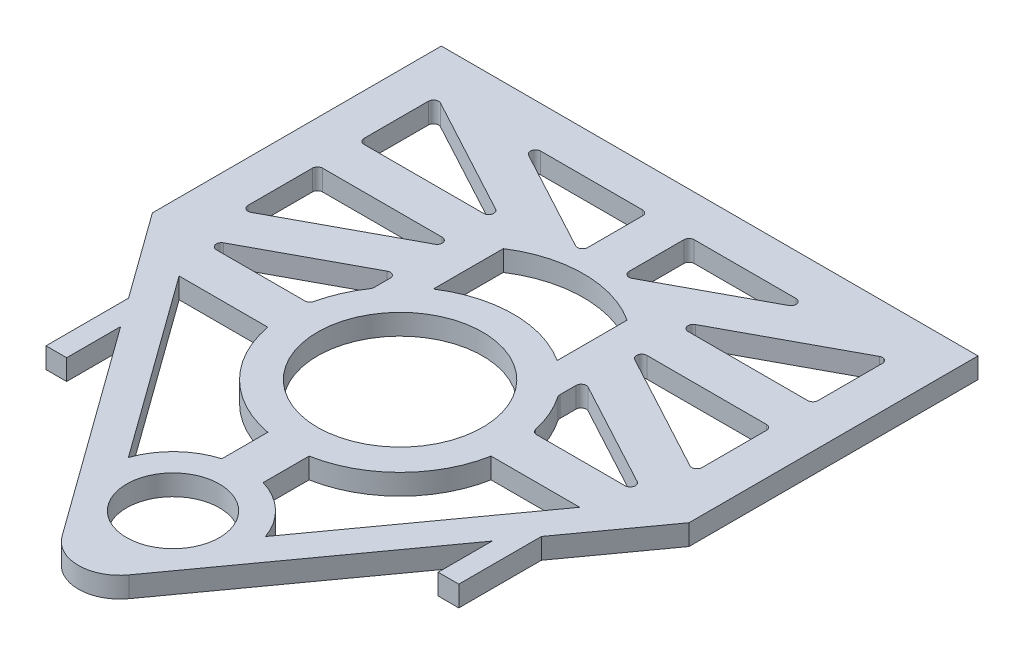
SolidWorks part; units mm, degrees
ref_plane "Front Plane" through (0, 0, 0) normal (0, 0, 1) x (1, 0, 0)
ref_plane "Top Plane" through (0, 0, 0) normal (0, 1, 0) x (1, 0, 0)
ref_plane "Right Plane" through (0, 0, 0) normal (1, 0, 0) x (0, 0, -1)
sketch "Sketch1" plane through (0, 0, 0) normal (0, 1, 0) x (1, 0, 0)
  line L0 (-82.55, -44.45) -> (-10.2956, -144.4945)
  line L2 (-82.55, -44.45) -> (-82.55, 44.45)
  line L3 (-82.55, 44.45) -> (82.55, 44.45)
  line L4 (82.55, -44.45) -> (82.55, 44.45)
  line L5 (-82.55, -44.45) -> (82.55, 44.45) construction
  line L6 (-82.55, 44.45) -> (82.55, -44.45) construction
  line L7 (10.2956, -144.4945) -> (82.55, -44.45)
  line L8 (0, 44.45) -> (0, -158.75) construction
  arc A0 (-10.2956, -144.4945) -> (10.2956, -144.4945) centre (0, -137.0588) ccw
  point P0 (0, 0)
  dimension "D3" = 12.7
  dimension "D1" = 165.1
  dimension "D2" = 88.9
  dimension "D4" = 203.2
extrude "Boss-Extrude1" add sketch "Sketch1" along normal blind 6.35
sketch "Sketch4" plane through (0, 6.35, 0) normal (0, 1, 0) x (1, 0, 0)
  line L0 (-63.5, -70.8269) -> (-63.5, -96.2269)
  line L1 (-82.55, -44.45) -> (-10.2956, -144.4945) construction
  line L2 (0, -149.7588) -> (0, 44.45) construction
  line L3 (82.55, 44.45) -> (-82.55, 44.45) construction
  line L4 (-63.5, -70.8269) -> (-57.15, -79.6192)
  line L5 (-57.15, -79.6192) -> (-57.15, -96.2269)
  line L6 (-57.15, -96.2269) -> (-63.5, -96.2269)
  line L7 (57.15, -96.2269) -> (63.5, -96.2269)
  line L8 (57.15, -79.6192) -> (57.15, -96.2269)
  line L9 (63.5, -70.8269) -> (57.15, -79.6192)
  line L10 (63.5, -70.8269) -> (63.5, -96.2269)
  arc A0 (-10.2956, -144.4945) -> (10.2956, -144.4945) centre (0, -137.0588) ccw construction
  point P18 (0, 0)
  dimension "D1" = 6.35
  dimension "D2" = 25.4
  dimension "D3" = 127
extrude "Boss-Extrude2" add sketch "Sketch4" against normal up to surface (6.35 mm away) up to face at (0, 0, 49.0422)
sketch "Sketch2" plane through (0, 6.35, 0) normal (0, 1, 0) x (1, 0, 0)
  line L0 (-82.55, 0) -> (82.55, 0) construction
  line L1 (-82.55, 44.45) -> (-82.55, -44.45) construction
  line L2 (82.55, -44.45) -> (82.55, 44.45) construction
  line L3 (0, 0) -> (-82.55, 44.45) construction
  line L4 (82.55, 44.45) -> (-82.55, 44.45) construction
  line L5 (0, 44.45) -> (0, -149.7588) construction
  line L6 (-39.2738, 31.75) -> (-7.9375, 31.75)
  line L7 (-6.35, 30.1625) -> (-6.35, 13.2891)
  line L8 (-8.6901, 11.8914) -> (-40.0265, 28.7648)
  line L9 (-69.85, 27.7417) -> (-69.85, 7.9375)
  line L10 (-68.2625, 6.35) -> (-31.4833, 6.35)
  line L11 (-30.7307, 9.3352) -> (-67.5099, 29.1394)
  line L30 (-82.55, -44.45) -> (82.55, -44.45) construction
  line L36 (10.2956, -144.4945) -> (57.15, -79.6192) construction
  line L37 (-51.3603, -50.8) -> (-9.8425, -50.8)
  line L38 (-8.255, -52.3875) -> (-8.255, -98.8766)
  line L39 (-52.6473, -53.317) -> (-16.5965, -103.2335)
  line L40 (-82.55, -44.45) -> (-63.5, -70.8269) construction
  line L41 (51.3603, -50.8) -> (9.8425, -50.8)
  line L42 (8.255, -52.3875) -> (8.255, -98.8766)
  line L43 (52.6473, -53.317) -> (16.5965, -103.2335)
  line L44 (30.7307, 9.3352) -> (67.5099, 29.1394)
  line L45 (68.2625, 6.35) -> (31.4833, 6.35)
  line L46 (69.85, 27.7417) -> (69.85, 7.9375)
  line L47 (6.35, 30.1625) -> (6.35, 13.2891)
  line L48 (8.6901, 11.8914) -> (40.0265, 28.7648)
  line L49 (39.2738, 31.75) -> (7.9375, 31.75)
  line L50 (-30.7307, -9.3352) -> (-67.5099, -29.1394)
  line L51 (-68.2625, -6.35) -> (-31.4833, -6.35)
  line L52 (-69.85, -27.7417) -> (-69.85, -7.9375)
  line L53 (-6.35, -30.1625) -> (-6.35, -13.2891)
  line L54 (-8.6901, -11.8914) -> (-40.0265, -28.7648)
  line L55 (-39.2738, -31.75) -> (-7.9375, -31.75)
  line L56 (39.2738, -31.75) -> (7.9375, -31.75)
  line L57 (8.6901, -11.8914) -> (40.0265, -28.7648)
  line L58 (6.35, -30.1625) -> (6.35, -13.2891)
  line L59 (69.85, -27.7417) -> (69.85, -7.9375)
  line L60 (68.2625, -6.35) -> (31.4833, -6.35)
  line L61 (30.7307, -9.3352) -> (67.5099, -29.1394)
  arc A0 (-10.2956, -144.4945) -> (10.2956, -144.4945) centre (0, -137.0588) ccw construction
  circle A1 centre (0, -120.65) radius 14.2875
  circle A2 centre (0, -120.65) radius 22.3072 construction
  arc A3 (-14.2924, -103.5229) -> (-9.1886, -100.3232) centre (0, -120.65) cw
  arc A4 (14.2924, -103.5229) -> (9.1886, -100.3232) centre (0, -120.65) ccw
  arc A5 (-6.35, 13.2891) -> (-8.6901, 11.8914) centre (-7.9375, 13.2891) cw
  arc A6 (-7.9375, 31.75) -> (-6.35, 30.1625) centre (-7.9375, 30.1625) cw
  arc A7 (-39.2738, 31.75) -> (-40.0265, 28.7648) centre (-39.2738, 30.1625) ccw
  arc A8 (-31.4833, 6.35) -> (-30.7307, 9.3352) centre (-31.4833, 7.9375) ccw
  arc A9 (-69.85, 7.9375) -> (-68.2625, 6.35) centre (-68.2625, 7.9375) ccw
  arc A10 (-69.85, 27.7417) -> (-67.5099, 29.1394) centre (-68.2625, 27.7417) cw
  arc A11 (31.4833, 6.35) -> (30.7307, 9.3352) centre (31.4833, 7.9375) cw
  arc A12 (69.85, 7.9375) -> (68.2625, 6.35) centre (68.2625, 7.9375) cw
  arc A13 (69.85, 27.7417) -> (67.5099, 29.1394) centre (68.2625, 27.7417) ccw
  arc A14 (7.9375, 31.75) -> (6.35, 30.1625) centre (7.9375, 30.1625) ccw
  arc A15 (6.35, 13.2891) -> (8.6901, 11.8914) centre (7.9375, 13.2891) ccw
  arc A16 (39.2738, 31.75) -> (40.0265, 28.7648) centre (39.2738, 30.1625) cw
  arc A17 (-69.85, -7.9375) -> (-68.2625, -6.35) centre (-68.2625, -7.9375) cw
  arc A18 (-69.85, -27.7417) -> (-67.5099, -29.1394) centre (-68.2625, -27.7417) ccw
  arc A19 (-31.4833, -6.35) -> (-30.7307, -9.3352) centre (-31.4833, -7.9375) cw
  arc A20 (-6.35, -13.2891) -> (-8.6901, -11.8914) centre (-7.9375, -13.2891) ccw
  arc A21 (-7.9375, -31.75) -> (-6.35, -30.1625) centre (-7.9375, -30.1625) ccw
  arc A22 (-39.2738, -31.75) -> (-40.0265, -28.7648) centre (-39.2738, -30.1625) cw
  arc A23 (39.2738, -31.75) -> (40.0265, -28.7648) centre (39.2738, -30.1625) ccw
  arc A24 (6.35, -13.2891) -> (8.6901, -11.8914) centre (7.9375, -13.2891) cw
  arc A25 (7.9375, -31.75) -> (6.35, -30.1625) centre (7.9375, -30.1625) cw
  arc A26 (69.85, -27.7417) -> (67.5099, -29.1394) centre (68.2625, -27.7417) cw
  arc A27 (69.85, -7.9375) -> (68.2625, -6.35) centre (68.2625, -7.9375) ccw
  arc A28 (31.4833, -6.35) -> (30.7307, -9.3352) centre (31.4833, -7.9375) ccw
  arc A29 (51.3603, -50.8) -> (52.6473, -53.317) centre (51.3603, -52.3875) cw
  arc A30 (9.8425, -50.8) -> (8.255, -52.3875) centre (9.8425, -52.3875) ccw
  arc A31 (14.2924, -103.5229) -> (16.5965, -103.2335) centre (15.3095, -102.304) ccw
  arc A32 (8.255, -98.8766) -> (9.1886, -100.3232) centre (9.8425, -98.8766) ccw
  arc A33 (-8.255, -98.8766) -> (-9.1886, -100.3232) centre (-9.8425, -98.8766) cw
  arc A34 (-16.5965, -103.2335) -> (-14.2924, -103.5229) centre (-15.3095, -102.304) ccw
  arc A35 (-9.8425, -50.8) -> (-8.255, -52.3875) centre (-9.8425, -52.3875) cw
  arc A36 (-51.3603, -50.8) -> (-52.6473, -53.317) centre (-51.3603, -52.3875) ccw
  point P63 (-6.35, 10.6313)
  point P65 (-6.35, 31.75)
  point P68 (-45.5705, 31.75)
  point P71 (-25.1867, 6.35)
  point P74 (-69.85, 6.35)
  point P77 (-69.85, 30.3995)
  point P117 (54.4651, -50.8)
  point P120 (8.255, -50.8)
  point P123 (15.5612, -104.6669)
  point P126 (8.255, -99.9264)
  point P129 (-8.255, -99.9264)
  point P132 (-15.5612, -104.6669)
  point P135 (-8.255, -50.8)
  point P138 (-54.4651, -50.8)
  dimension "D7" = 28.575
  dimension "D9" = 19.05
  dimension "D12" = 1.5875
  dimension "D13" = 1.5875
  dimension "D1" = 12.7
  dimension "D2" = 6.35
  dimension "D3" = 6.35
  dimension "D4" = 12.7
  dimension "D5" = 6.35
  dimension "D6" = 6.35
  dimension "D8" = 76.2
  dimension "D10" = 8.255
  dimension "D11" = 6.35
extrude "Cut-Extrude1" [suppressed] cut sketch "Sketch2" against normal up to next contours A19 L51 A17 L52 A18 L50 | A10 L9 A9 L10 A8 L11 | L6 A7 L8 A5 L7 A6 | A16 L49 A14 L47 A15 L48 | L46 A13 L44 A11 L45 A12 | L60 A28 L61 A26 L59 A27 | A25 L56 A23 L57 A24 L58 | A22 L55 A21 L53 A20 L54 | L37 A36 L39 A34 A3 A33 L38 A35 | L42 A32 A4 A31 L43 A29 L41 A30 | A1
sketch "Sketch3" plane through (0, 6.35, 0) normal (0, 1, 0) x (1, 0, 0)
  line L0 (-82.55, 0) -> (82.55, 0) construction
  line L1 (-82.55, 44.45) -> (-82.55, -44.45) construction
  line L2 (82.55, -44.45) -> (82.55, 44.45) construction
  line L3 (-82.55, 44.45) -> (0, 0) construction
  line L4 (82.55, 44.45) -> (-82.55, 44.45) construction
  line L5 (0, 44.45) -> (0, 0) construction
  line L6 (-40.0265, 28.7648) -> (-8.6901, 11.8914)
  line L7 (-6.35, 13.2891) -> (-6.35, 30.1625)
  line L8 (-7.9375, 31.75) -> (-39.2738, 31.75)
  line L9 (-69.85, 27.7417) -> (-69.85, 7.9375)
  line L10 (-68.2625, 6.35) -> (-31.4833, 6.35)
  line L11 (-30.7307, 9.3352) -> (-67.5099, 29.1394)
  line L12 (7.9375, 31.75) -> (39.2738, 31.75)
  line L13 (6.35, 13.2891) -> (6.35, 30.1625)
  line L14 (40.0265, 28.7648) -> (8.6901, 11.8914)
  line L15 (30.7307, 9.3352) -> (67.5099, 29.1394)
  line L16 (68.2625, 6.35) -> (31.4833, 6.35)
  line L17 (69.85, 27.7417) -> (69.85, 7.9375)
  line L18 (69.85, -27.7417) -> (69.85, -7.9375)
  line L19 (68.2625, -6.35) -> (31.4833, -6.35)
  line L20 (30.7307, -9.3352) -> (67.5099, -29.1394)
  line L21 (-30.7307, -9.3352) -> (-67.5099, -29.1394)
  line L22 (-68.2625, -6.35) -> (-31.4833, -6.35)
  line L23 (-69.85, -27.7417) -> (-69.85, -7.9375)
  line L24 (-77.9639, -50.8) -> (77.9639, -50.8) construction
  line L25 (0, 0) -> (-82.55, -44.45) construction
  line L30 (0, -50.8) -> (0, -120.65) construction
  line L31 (-6.35, -85.1429) -> (-6.35, -99.2657)
  line L32 (-61.6284, -57.15) -> (-34.3429, -57.15)
  line L33 (-61.6284, -57.15) -> (-21.0661, -113.3131)
  line L34 (-82.55, -44.45) -> (-63.5, -70.8269) construction
  line L35 (6.35, -85.1429) -> (6.35, -99.2657)
  line L36 (61.6284, -57.15) -> (21.0661, -113.3131)
  line L37 (61.6284, -57.15) -> (34.3429, -57.15)
  line L38 (-19.05, -21.5279) -> (-19.05, 0)
  line L39 (19.05, -21.5279) -> (19.05, 0)
  line L40 (-82.55, -44.45) -> (-63.5, -70.8269) construction
  line L41 (-62.8595, -44.45) -> (-35.6393, -44.45)
  line L42 (-63.6122, -41.4648) -> (-30.9151, -23.8587)
  line L43 (-28.575, -25.2564) -> (-28.575, -30.2236)
  line L44 (28.575, -25.2564) -> (28.575, -30.2236)
  line L45 (62.8595, -44.45) -> (35.6393, -44.45)
  line L46 (63.6122, -41.4648) -> (30.9151, -23.8587)
  arc A0 (-8.6901, 11.8914) -> (-6.35, 13.2891) centre (-7.9375, 13.2891) ccw
  arc A1 (-6.35, 30.1625) -> (-7.9375, 31.75) centre (-7.9375, 30.1625) ccw
  arc A2 (-40.0265, 28.7648) -> (-39.2738, 31.75) centre (-39.2738, 30.1625) cw
  arc A3 (-31.4833, 6.35) -> (-30.7307, 9.3352) centre (-31.4833, 7.9375) ccw
  arc A4 (-69.85, 7.9375) -> (-68.2625, 6.35) centre (-68.2625, 7.9375) ccw
  arc A5 (-69.85, 27.7417) -> (-67.5099, 29.1394) centre (-68.2625, 27.7417) cw
  arc A6 (6.35, 30.1625) -> (7.9375, 31.75) centre (7.9375, 30.1625) cw
  arc A7 (40.0265, 28.7648) -> (39.2738, 31.75) centre (39.2738, 30.1625) ccw
  arc A8 (8.6901, 11.8914) -> (6.35, 13.2891) centre (7.9375, 13.2891) cw
  arc A9 (69.85, 7.9375) -> (68.2625, 6.35) centre (68.2625, 7.9375) cw
  arc A10 (69.85, 27.7417) -> (67.5099, 29.1394) centre (68.2625, 27.7417) ccw
  arc A11 (31.4833, 6.35) -> (30.7307, 9.3352) centre (31.4833, 7.9375) cw
  arc A12 (31.4833, -6.35) -> (30.7307, -9.3352) centre (31.4833, -7.9375) ccw
  arc A13 (69.85, -27.7417) -> (67.5099, -29.1394) centre (68.2625, -27.7417) cw
  arc A14 (69.85, -7.9375) -> (68.2625, -6.35) centre (68.2625, -7.9375) ccw
  arc A15 (-69.85, -27.7417) -> (-67.5099, -29.1394) centre (-68.2625, -27.7417) ccw
  arc A16 (-69.85, -7.9375) -> (-68.2625, -6.35) centre (-68.2625, -7.9375) cw
  arc A17 (-31.4833, -6.35) -> (-30.7307, -9.3352) centre (-31.4833, -7.9375) cw
  circle A18 centre (0, -50.8) radius 25.4
  circle A19 centre (0, -50.8) radius 34.925 construction
  arc A29 (-28.8511, -31.1183) -> (-34.0898, -43.2076) centre (0, -50.8) ccw
  circle A30 centre (0, -120.65) radius 14.2875 construction
  circle A31 centre (0, -120.65) radius 14.2875
  circle A32 centre (0, -120.65) radius 22.3072 construction
  circle A33 centre (0, -120.65) radius 22.3072 construction
  arc A34 (-34.3429, -57.15) -> (-6.35, -85.1429) centre (0, -50.8) ccw
  arc A35 (-6.35, -99.2657) -> (-21.0661, -113.3131) centre (0, -120.65) ccw
  arc A36 (6.35, -99.2657) -> (21.0661, -113.3131) centre (0, -120.65) cw
  arc A37 (34.3429, -57.15) -> (6.35, -85.1429) centre (0, -50.8) cw
  arc A38 (19.05, -21.5279) -> (-19.05, -21.5279) centre (0, -50.8) ccw
  arc A39 (-19.05, 0) -> (19.05, 0) centre (0, -29.2721) cw
  arc A40 (-35.6393, -44.45) -> (-34.0898, -43.2076) centre (-35.6393, -42.8625) ccw
  arc A41 (-28.575, -30.2236) -> (-28.8511, -31.1183) centre (-30.1625, -30.2236) cw
  arc A42 (-30.9151, -23.8587) -> (-28.575, -25.2564) centre (-30.1625, -25.2564) cw
  arc A43 (-62.8595, -44.45) -> (-63.6122, -41.4648) centre (-62.8595, -42.8625) cw
  arc A44 (28.575, -30.2236) -> (28.8511, -31.1183) centre (30.1625, -30.2236) ccw
  arc A45 (30.9151, -23.8587) -> (28.575, -25.2564) centre (30.1625, -25.2564) ccw
  arc A46 (28.8511, -31.1183) -> (34.0898, -43.2076) centre (0, -50.8) cw
  arc A47 (35.6393, -44.45) -> (34.0898, -43.2076) centre (35.6393, -42.8625) cw
  arc A48 (62.8595, -44.45) -> (63.6122, -41.4648) centre (62.8595, -42.8625) ccw
  point P76 (0, 0)
  point P82 (-34.3429, -44.45)
  point P85 (-28.575, -30.7195)
  point P115 (0, -15.875)
  dimension "D7" = 1.5875
  dimension "D8" = 50.8
  dimension "D9" = 9.525
  dimension "D12" = 6.35
  dimension "D13" = 9.525
  dimension "D16" = 38.1
  dimension "D17" = 50.8
  dimension "D18" = 1.5875
  dimension "D1" = 12.7
  dimension "D2" = 6.35
  dimension "D3" = 6.35
  dimension "D4" = 6.35
  dimension "D5" = 12.7
  dimension "D6" = 6.35
  dimension "D10" = 9.525
  dimension "D11" = 6.35
  dimension "D14" = 6.35
  dimension "D15" = 6.35
extrude "Cut-Extrude2" cut sketch "Sketch3" against normal up to next
